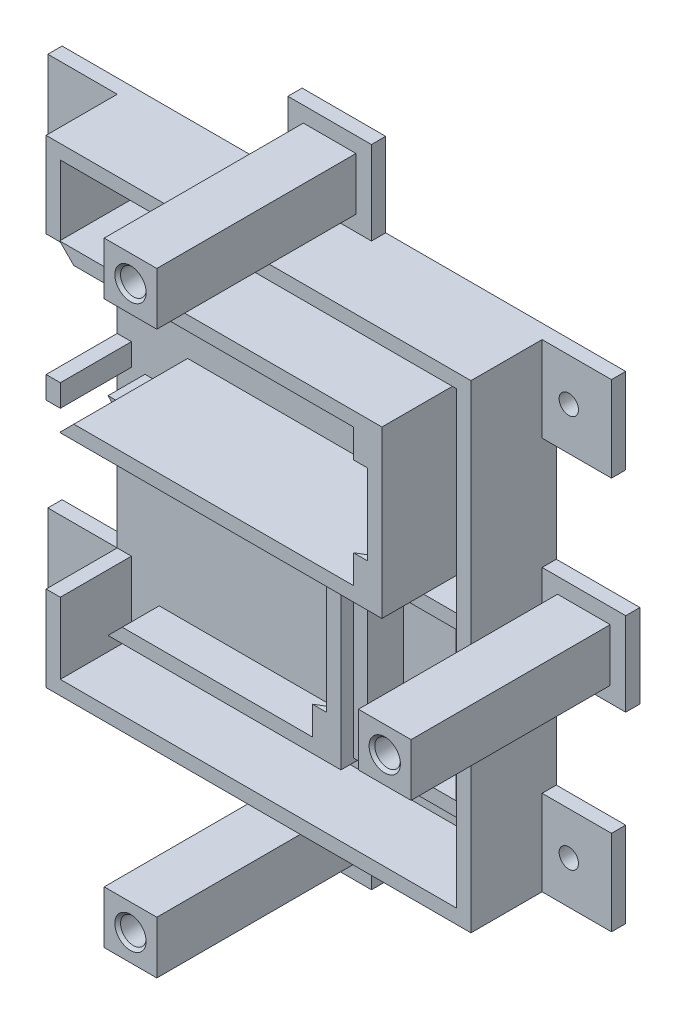
SolidWorks part; units mm, degrees
note: The reader was unsure of these and kept them because the rebuilt part matched: shared geometry of "Sketch1<6>", "Sketch6<4>", "Sketch6<9>".
material "Brass"
ref_plane "Front Plane" through (0, 0, 0) normal (0, 0, 1) x (1, 0, 0)
ref_plane "Top Plane" through (0, 0, 0) normal (0, 1, 0) x (1, 0, 0)
ref_plane "Right Plane" through (0, 0, 0) normal (1, 0, 0) x (0, 0, -1)
sketch "Sketch1" plane through (0, 0, 0) normal (0, 0, 1) x (1, 0, 0)
  line L0 (-37.335, 29.835) -> (-37.335, 39.085) construction
  line L5 (-49.525, -42.025) -> (-34.525, -42.025)
  line L6 (-49.525, -42.025) -> (-49.525, -27.025)
  line L7 (-49.525, 42.025) -> (-34.525, 42.025)
  line L8 (-49.525, 42.025) -> (-49.525, 27.025)
  line L9 (-49.525, 27.025) -> (-34.525, 27.025)
  line L10 (-34.525, 42.025) -> (-34.525, 27.025)
  line L11 (-42.025, 27.025) -> (-42.025, 42.025) construction
  line L12 (-49.525, 34.525) -> (-34.525, 34.525) construction
  line L13 (49.525, 42.025) -> (34.525, 42.025)
  line L14 (49.525, 42.025) -> (49.525, 27.025)
  line L15 (49.525, 27.025) -> (34.525, 27.025)
  line L16 (34.525, 42.025) -> (34.525, 27.025)
  line L17 (42.025, 27.025) -> (42.025, 42.025) construction
  line L18 (49.525, 34.525) -> (34.525, 34.525) construction
  line L19 (49.525, -42.025) -> (34.525, -42.025)
  line L20 (49.525, -42.025) -> (49.525, -27.025)
  line L21 (49.525, -27.025) -> (34.525, -27.025)
  line L22 (34.525, -42.025) -> (34.525, -27.025)
  line L23 (42.025, -27.025) -> (42.025, -42.025) construction
  line L24 (49.525, -34.525) -> (34.525, -34.525) construction
  line L25 (-49.525, -27.025) -> (-34.525, -27.025)
  line L26 (-34.525, -42.025) -> (-34.525, -27.025)
  line L27 (-42.025, -27.025) -> (-42.025, -42.025) construction
  line L28 (-49.525, -34.525) -> (-34.525, -34.525) construction
  line L29 (-37.335, 42.025) -> (37.335, 42.025)
  line L30 (-37.335, 42.025) -> (-37.335, -42.025)
  line L31 (-37.335, -42.025) -> (37.335, -42.025)
  line L32 (37.335, 42.025) -> (37.335, -42.025)
  line L33 (0, -42.025) -> (0, 42.025) construction
  line L34 (-37.335, 0) -> (37.335, 0) construction
  line L35 (37.335, -29.835) -> (37.335, -39.085) construction
  line L36 (-34.835, 39.525) -> (34.835, 39.525)
  line L37 (34.835, 39.525) -> (34.835, -39.525)
  line L38 (-34.835, -39.525) -> (34.835, -39.525)
  line L39 (-34.835, 39.525) -> (-34.835, -39.525)
  line L41 (-32.335, 1.725) -> (-29.835, -0.775)
  line L42 (-29.835, -32.025) -> (-32.335, -34.525)
  line L43 (-29.835, -32.025) -> (-29.835, -0.775) construction
  line L44 (-24.835, 32.025) -> (-27.335, 34.525)
  line L46 (-29.835, 8.125) -> (-29.835, -0.775)
  line L47 (-29.835, -32.025) -> (-29.835, -0.775)
  line L48 (-27.335, 34.525) -> (-27.335, 5.625)
  line L49 (-27.335, 5.625) -> (29.065, 5.625)
  line L50 (29.065, 5.625) -> (29.065, 34.525)
  line L51 (29.065, 34.525) -> (-27.335, 34.525)
  line L53 (-27.335, 5.625) -> (29.065, 5.625)
  line L54 (29.065, 5.625) -> (29.065, 34.525)
  line L55 (29.065, 34.525) -> (-27.335, 34.525)
  line L56 (-32.335, 1.725) -> (-37.335, 1.725)
  line L57 (-27.335, 34.525) -> (-37.335, 34.525)
  line L58 (-27.335, 34.525) -> (-27.335, 5.625)
  line L59 (-27.335, 5.625) -> (-37.335, 5.625)
  line L60 (-32.335, -34.525) -> (8.365, -34.525)
  line L61 (8.365, -34.525) -> (8.365, 1.725)
  line L62 (8.365, 1.725) -> (-32.335, 1.725)
  line L63 (-32.335, 1.725) -> (-32.335, -34.525)
  line L64 (-32.335, -34.525) -> (8.365, -34.525)
  line L65 (8.365, -34.525) -> (8.365, 1.725)
  line L66 (8.365, 1.725) -> (-32.335, 1.725)
  line L68 (-37.335, 34.525) -> (-37.335, 5.625)
  line L69 (-32.335, 5.625) -> (-32.335, 34.525) construction
  line L70 (-27.335, 20.075) -> (-37.335, 20.075) construction
  line L71 (-32.335, -34.525) -> (-37.335, -34.525)
  line L72 (-37.335, -34.525) -> (-37.335, -34.1821)
  line L73 (-37.335, -34.1821) -> (-37.335, 0)
  line L76 (26.565, 29.525) -> (-24.835, 29.525)
  line L77 (26.565, 29.525) -> (-24.835, 29.525)
  line L96 (7.345, -42.025) -> (-7.345, -42.025)
  line L97 (7.345, -42.025) -> (7.345, -56.715)
  line L98 (7.345, -56.715) -> (-7.345, -56.715)
  line L99 (-7.345, -42.025) -> (-7.345, -56.715)
  line L100 (0, -56.715) -> (0, -42.025) construction
  line L101 (7.345, -49.37) -> (-7.345, -49.37) construction
  line L102 (37.335, -7.345) -> (52.025, -7.345)
  line L103 (37.335, -7.345) -> (37.335, 7.345)
  line L104 (37.335, 7.345) -> (52.025, 7.345)
  line L105 (52.025, -7.345) -> (52.025, 7.345)
  line L106 (44.68, 7.345) -> (44.68, -7.345) construction
  line L107 (37.335, 0) -> (52.025, 0) construction
  line L108 (7.345, 42.025) -> (-7.345, 42.025)
  line L109 (7.345, 42.025) -> (7.345, 56.715)
  line L110 (7.345, 56.715) -> (-7.345, 56.715)
  line L111 (-7.345, 42.025) -> (-7.345, 56.715)
  line L112 (0, 56.715) -> (0, 42.025) construction
  line L113 (7.345, 49.37) -> (-7.345, 49.37) construction
  circle A0 centre (-42.025, 34.525) radius 1.7
  circle A1 centre (-42.025, -34.525) radius 1.7
  circle A2 centre (42.025, 34.525) radius 1.7
  circle A3 centre (42.025, -34.525) radius 1.7
  point P52 (42.025, 34.525)
  point P81 (42.025, -34.525)
  point P92 (0, 49.37)
  point P100 (-42.025, -34.525)
  point P109 (0, -49.37)
  point P162 (44.68, 0)
  point P179 (0, 0)
  point P250 (-42.025, 34.525)
  point P655 (-32.335, 20.075)
  dimension "D9" = 3.4
  dimension "D10" = 3.4
  dimension "D11" = 3.4
  dimension "D12" = 3.4
  dimension "D1" = 15
  dimension "D2" = 15
  dimension "D3" = 15
  dimension "D4" = 15
  dimension "D5" = 15
  dimension "D6" = 15
  dimension "D7" = 15
  dimension "D8" = 15
  dimension "D17" = 14.69
  dimension "D18" = 14.69
  dimension "D19" = 14.69
  dimension "D20" = 14.69
  dimension "D21" = 14.69
  dimension "D22" = 14.69
  dimension "D13" = 2.5
  dimension "D14" = 2.5
  dimension "D15" = 2.5
  dimension "D16" = 2.5
extrude "Boss-Extrude1" add sketch "Sketch1" along normal blind 2.5
extrude "Boss-Extrude3" add sketch "Sketch1<6>" along normal blind 15 contours L38 L26 L31 L22 | L10 L36 L16 L29 | L15 L37 L21 L32 | L39 L59 L30 L56 | L36 L37 L15 L32 L13 L16 | L38 L22 L19 L32 L21 L37 | L39 L71 L30 L5 L26 L38 | L71 L39 L25 L30 | L39 L57 L30 L9 | L57 L39 L36 L10 L7 L30
sketch "Sketch1<6>" plane through (0, 0, 0) normal (0, 0, 1) x (1, 0, 0) same geometry as "Sketch1"
sketch "Sketch6" plane through (0, 0, 2.5) normal (0, 0, 1) x (1, 0, 0)
  line L4 (33.455, -0.855) -> (10.435, -0.855)
  line L5 (10.435, -0.855) -> (10.435, -31.945)
  line L6 (10.435, -31.945) -> (33.455, -31.945)
  line L7 (33.455, -31.945) -> (33.455, -0.855)
  line L8 (-24.955, 32.145) -> (-24.955, 8.005)
  line L9 (-24.955, 8.005) -> (26.685, 8.005)
  line L10 (26.685, 8.005) -> (26.685, 32.145)
  line L11 (26.685, 32.145) -> (-24.955, 32.145)
  line L12 (-24.955, 32.145) -> (-24.955, 8.005) construction
  line L13 (-24.955, 8.005) -> (26.685, 8.005) construction
  line L14 (26.685, 8.005) -> (26.685, 32.145) construction
  line L15 (26.685, 32.145) -> (-24.955, 32.145) construction
  line L16 (29.185, 34.645) -> (-27.455, 34.645)
  line L17 (-27.455, 34.645) -> (-27.455, 5.505)
  line L18 (-27.455, 5.505) -> (29.185, 5.505)
  line L19 (29.185, 5.505) -> (29.185, 34.645)
  line L20 (-29.955, -32.145) -> (5.985, -32.145)
  line L21 (5.985, -32.145) -> (5.985, -0.655)
  line L22 (5.985, -0.655) -> (-29.955, -0.655)
  line L23 (-29.955, -0.655) -> (-29.955, -32.145)
  line L24 (-29.955, -32.145) -> (5.985, -32.145) construction
  line L25 (5.985, -32.145) -> (5.985, -0.655) construction
  line L26 (5.985, -0.655) -> (-29.955, -0.655) construction
  line L27 (-29.955, -0.655) -> (-29.955, -32.145) construction
  line L28 (8.485, 1.845) -> (-32.455, 1.845)
  line L29 (-32.455, 1.845) -> (-32.455, -34.645)
  line L30 (-32.455, -34.645) -> (8.485, -34.645)
  line L31 (8.485, -34.645) -> (8.485, 1.845)
  line L32 (-27.455, 34.645) -> (-24.955, 32.145)
  line L33 (-27.455, 5.505) -> (-24.955, 8.005)
  line L34 (-32.455, 1.845) -> (-29.955, -0.655)
  line L35 (-32.455, -34.645) -> (-29.955, -32.145)
  line L36 (-24.955, 32.145) -> (-24.955, 8.005)
  line L37 (-29.955, -0.655) -> (-29.955, -32.145)
  line L38 (30.955, -29.445) -> (30.955, -3.355)
  line L39 (-24.955, 32.145) -> (26.685, 32.145)
  line L40 (-24.955, 32.145) -> (-24.955, 8.005)
  line L41 (-24.955, 8.005) -> (26.685, 8.005)
  line L42 (26.685, 32.145) -> (26.685, 8.005)
  line L43 (0.865, 8.005) -> (0.865, 32.145) construction
  line L44 (-24.955, 20.075) -> (26.685, 20.075) construction
  line L45 (-29.955, -0.655) -> (5.985, -0.655)
  line L46 (-29.955, -0.655) -> (-29.955, -32.145)
  line L47 (-29.955, -32.145) -> (5.985, -32.145)
  line L48 (5.985, -0.655) -> (5.985, -32.145)
  line L49 (-11.985, -32.145) -> (-11.985, -0.655) construction
  line L50 (-29.955, -16.4) -> (5.985, -16.4) construction
  line L51 (30.955, -3.355) -> (12.935, -3.355)
  line L52 (12.935, -3.355) -> (12.935, -29.445)
  line L53 (12.935, -29.445) -> (30.955, -29.445)
  line L54 (30.955, -29.445) -> (30.955, -3.355)
  line L55 (30.955, -3.355) -> (12.935, -3.355)
  line L56 (12.935, -3.355) -> (12.935, -29.445)
  line L57 (12.935, -29.445) -> (30.955, -29.445)
  point P281 (0.865, 20.075)
  point P454 (-11.985, -16.4)
  dimension "D1" = 0.12
  dimension "D2" = 0.12
  dimension "D3" = 2.5
  dimension "D4" = 0.12
  dimension "D5" = 2.5
extrude "Boss-Extrude8" add sketch "Sketch6" along normal blind 20 contours L39 L42 L41 L33 L18 L19 L16 L32
extrude "Boss-Extrude9" add sketch "Sketch6<4>" along normal blind 6.5 contours L45 L48 L47 L35 L30 L31 L28 L34
sketch "Sketch6<4>" plane through (0, 0, 2.5) normal (0, 0, 1) x (1, 0, 0) same geometry as "Sketch6"
extrude "Boss-Extrude13" add sketch "Sketch6<9>" along normal blind 6.28 contours L6 L7 L4 L5 L57 L56 L55 L54
sketch "Sketch6<9>" plane through (0, 0, 2.5) normal (0, 0, 1) x (1, 0, 0) same geometry as "Sketch6"
sketch "Sketch7" plane through (0, 0, 2.5) normal (0, 0, 1) x (1, 0, 0)
  line L0 (-7.345, 56.715) -> (7.345, 42.025) construction
  line L1 (7.345, 42.025) -> (7.345, 56.715) construction
  line L2 (7.345, 56.715) -> (-7.345, 42.025) construction
  line L3 (-7.345, 42.025) -> (7.345, 42.025) construction
  line L4 (37.335, 42.025) -> (-37.335, 42.025) construction
  line L5 (52.025, -7.345) -> (37.335, 7.345) construction
  line L6 (37.335, 7.345) -> (52.025, 7.345) construction
  line L7 (52.025, 7.345) -> (37.335, -7.345) construction
  line L8 (37.335, 42.025) -> (37.335, -42.025) construction
  line L9 (37.335, -7.345) -> (37.335, 7.345) construction
  line L10 (-7.345, -42.025) -> (7.345, -56.715) construction
  line L11 (7.345, -56.715) -> (-7.345, -56.715) construction
  line L12 (-7.345, -56.715) -> (7.345, -42.025) construction
  line L13 (7.345, -42.025) -> (7.345, -56.715) construction
  line L14 (7.345, -42.025) -> (-7.345, -42.025) construction
  line L16 (-4.625, 53.995) -> (4.625, 53.995)
  line L17 (-4.625, 53.995) -> (-4.625, 44.745)
  line L18 (-4.625, 44.745) -> (4.625, 44.745)
  line L19 (4.625, 53.995) -> (4.625, 44.745)
  line L20 (-4.625, 53.995) -> (4.625, 44.745) construction
  line L21 (-4.625, 44.745) -> (4.625, 53.995) construction
  line L22 (40.055, 4.625) -> (49.305, 4.625)
  line L23 (40.055, 4.625) -> (40.055, -4.625)
  line L24 (40.055, -4.625) -> (49.305, -4.625)
  line L25 (49.305, 4.625) -> (49.305, -4.625)
  line L26 (40.055, 4.625) -> (49.305, -4.625) construction
  line L27 (40.055, -4.625) -> (49.305, 4.625) construction
  line L28 (-4.625, -44.745) -> (4.625, -44.745)
  line L29 (-4.625, -44.745) -> (-4.625, -53.995)
  line L30 (-4.625, -53.995) -> (4.625, -53.995)
  line L31 (4.625, -44.745) -> (4.625, -53.995)
  line L32 (-4.625, -44.745) -> (4.625, -53.995) construction
  line L33 (-4.625, -53.995) -> (4.625, -44.745) construction
  point P26 (0, 49.37)
  point P38 (44.68, 0)
  point P43 (0, -49.37)
  dimension "D1" = 9.25
  dimension "D2" = 9.25
  dimension "D3" = 9.25
  dimension "D4" = 9.25
  dimension "D5" = 9.25
  dimension "D6" = 9.25
extrude "Boss-Extrude14" add sketch "Sketch7" along normal blind 35
sketch "Sketch8" plane through (0, 0, 37.5) normal (0, 0, 1) x (1, 0, 0)
  line L0 (4.625, -53.995) -> (-4.625, -44.745) construction
  line L1 (-4.625, -44.745) -> (-4.625, -53.995) construction
  line L2 (-4.625, -53.995) -> (4.625, -44.745) construction
  line L3 (49.305, -4.625) -> (40.055, 4.625) construction
  line L4 (49.305, 4.625) -> (40.055, 4.625) construction
  line L5 (4.625, 44.745) -> (-4.625, 53.995) construction
  line L6 (4.625, 53.995) -> (-4.625, 53.995) construction
  circle A0 centre (0, -49.37) radius 2.25
  circle A1 centre (44.68, 0) radius 2.25
  circle A2 centre (0, 49.37) radius 2.25
  dimension "D1" = 4.5
  dimension "D2" = 4.5
  dimension "D3" = 4.5
extrude "Cut-Extrude1" cut sketch "Sketch8" against normal blind 6.2
chamfer "Chamfer1" distance 0.5 angle 45 3 edges at (2.25, 49.37, 37.5) (46.93, 0, 37.5) (2.25, -49.37, 37.5)
sketch "Sketch9" plane through (26.685, 0, 0) normal (-1, 0, 0) x (0, 0, 1)
  line L0 (21, 8.125) -> (21, 32.025) construction
  line L1 (22.5, 32.145) -> (21.13, 32.145)
  line L2 (22.5, 32.145) -> (22.5, 27.145)
  line L3 (22.5, 27.145) -> (21.13, 27.145)
  line L4 (21.13, 32.145) -> (21.13, 27.145)
  line L5 (21.815, 27.145) -> (21.815, 32.145) construction
  line L6 (22.5, 29.645) -> (21.13, 29.645) construction
  line L7 (22.5, 20.075) -> (21.13, 20.075) construction
  line L8 (22.5, 32.145) -> (22.5, 8.005) construction
  line L9 (22.5, 8.005) -> (21.13, 8.005)
  line L10 (21.13, 8.005) -> (21.13, 13.005)
  line L11 (22.5, 13.005) -> (21.13, 13.005)
  line L12 (22.5, 8.005) -> (22.5, 13.005)
  point P64 (21.815, 29.645)
  dimension "D1" = 0.13
  dimension "D2" = 5
extrude "Boss-Extrude15" add sketch "Sketch9" along normal blind 2.5
sketch "Sketch10" plane through (0, 27.145, 0) normal (0, 1, 0) x (1, 0, 0)
  line L0 (26.435, -21.13) -> (24.185, -22.5)
  line L3 (24.185, -22.5) -> (24.185, -21.13)
  line L5 (24.185, -21.13) -> (26.435, -21.13)
  line L8 (26.685, -21.13) -> (26.685, -22.5) construction
  dimension "D1" = 0.25
extrude "Cut-Extrude2" cut sketch "Sketch10" along normal blind 5
sketch "Sketch12" plane through (30.955, 0, 0) normal (-1, 0, 0) x (0, 0, 1)
  line L0 (7.28, -29.325) -> (7.28, -3.475) construction
  line L1 (8.78, -3.355) -> (7.4, -3.355)
  line L2 (8.78, -3.355) -> (8.78, -8.355)
  line L3 (8.78, -8.355) -> (7.4, -8.355)
  line L4 (7.4, -3.355) -> (7.4, -8.355)
  line L5 (8.09, -8.355) -> (8.09, -3.355) construction
  line L6 (8.78, -5.855) -> (7.4, -5.855) construction
  line L7 (8.78, -29.445) -> (7.4, -29.445)
  line L8 (8.78, -29.445) -> (8.78, -24.445)
  line L9 (8.78, -24.445) -> (7.4, -24.445)
  line L10 (7.4, -29.445) -> (7.4, -24.445)
  line L11 (8.09, -24.445) -> (8.09, -29.445) construction
  line L12 (8.78, -26.945) -> (7.4, -26.945) construction
  point P60 (8.09, -5.855)
  point P106 (8.09, -26.945)
  dimension "D1" = 0.12
  dimension "D2" = 0.12
  dimension "D3" = 5
  dimension "D4" = 5
extrude "Boss-Extrude16" add sketch "Sketch12" along normal blind 2.5
sketch "Sketch13" plane through (0, -8.355, 0) normal (0, -1, 0) x (1, 0, 0)
  line L0 (30.705, 7.4) -> (28.455, 8.78)
  line L1 (28.455, 7.4) -> (30.955, 7.4) construction
  line L2 (28.455, 8.78) -> (28.455, 7.4)
  line L3 (28.455, 7.4) -> (28.455, 8.78) construction
  line L4 (28.455, 7.4) -> (30.705, 7.4)
  line L5 (30.955, 7.4) -> (30.955, 8.78) construction
  dimension "D1" = 0.25
extrude "Cut-Extrude3" cut sketch "Sketch13" against normal blind 5
sketch "Sketch14" plane through (0, -24.445, 0) normal (0, 1, 0) x (1, 0, 0)
  line L0 (30.705, -7.4) -> (28.455, -8.78)
  line L1 (28.455, -7.4) -> (30.955, -7.4) construction
  line L2 (28.455, -8.78) -> (28.455, -7.4)
  line L3 (28.455, -8.78) -> (28.455, -7.4) construction
  line L4 (28.455, -7.4) -> (30.705, -7.4)
  line L5 (30.955, -8.78) -> (30.955, -7.4) construction
  dimension "D1" = 0.25
extrude "Cut-Extrude4" cut sketch "Sketch14" against normal blind 5
sketch "Sketch15" plane through (5.985, 0, 0) normal (-1, 0, 0) x (0, 0, 1)
  line L0 (9, -16.4) -> (7.8078, -16.4) construction
  line L1 (9, -0.655) -> (7.62, -0.655)
  line L2 (9, -0.655) -> (9, -5.655)
  line L3 (9, -5.655) -> (7.62, -5.655)
  line L4 (7.62, -0.655) -> (7.62, -5.655)
  line L5 (8.31, -5.655) -> (8.31, -0.655) construction
  line L6 (9, -3.155) -> (7.62, -3.155) construction
  line L7 (9, -0.655) -> (9, -32.145) construction
  line L8 (7.5, -32.025) -> (7.5, -0.775) construction
  line L9 (9, -32.145) -> (7.62, -32.145)
  line L10 (7.62, -32.145) -> (7.62, -27.145)
  line L11 (9, -32.145) -> (9, -27.145)
  line L12 (9, -27.145) -> (7.62, -27.145)
  point P68 (8.31, -3.155)
  dimension "D1" = 5
  dimension "D2" = 0.12
extrude "Boss-Extrude17" add sketch "Sketch15" along normal blind 2.5
sketch "Sketch16" plane through (0, -5.655, 0) normal (0, -1, 0) x (1, 0, 0)
  line L0 (3.485, 9) -> (3.485, 7.62)
  line L1 (3.485, 7.62) -> (3.485, 9) construction
  line L2 (3.485, 7.62) -> (5.735, 7.62)
  line L3 (3.485, 7.62) -> (5.985, 7.62) construction
  line L4 (5.735, 7.62) -> (3.485, 9)
  dimension "D1" = 0.25
extrude "Cut-Extrude5" cut sketch "Sketch16" against normal blind 5
sketch "Sketch17" plane through (0, -27.145, 0) normal (0, 1, 0) x (1, 0, 0)
  line L0 (3.485, -9) -> (3.485, -7.62)
  line L1 (3.485, -7.62) -> (5.735, -7.62)
  line L2 (3.485, -7.62) -> (5.985, -7.62) construction
  line L3 (5.735, -7.62) -> (3.485, -9)
  line L4 (5.985, -9) -> (5.985, -7.62) construction
  dimension "D1" = 0.25
extrude "Cut-Extrude6" cut sketch "Sketch17" against normal blind 5
sketch "Sketch18" plane through (0, 13.005, 0) normal (0, 1, 0) x (1, 0, 0)
  line L0 (24.185, -22.5) -> (24.185, -21.13)
  line L1 (24.185, -22.5) -> (24.185, -21.13) construction
  line L2 (24.185, -21.13) -> (26.435, -21.13)
  line L3 (24.185, -21.13) -> (26.685, -21.13) construction
  line L4 (26.435, -21.13) -> (24.185, -22.5)
  line L5 (26.685, -22.5) -> (26.685, -21.13) construction
  dimension "D1" = 0.25
extrude "Cut-Extrude7" cut sketch "Sketch18" against normal blind 5
